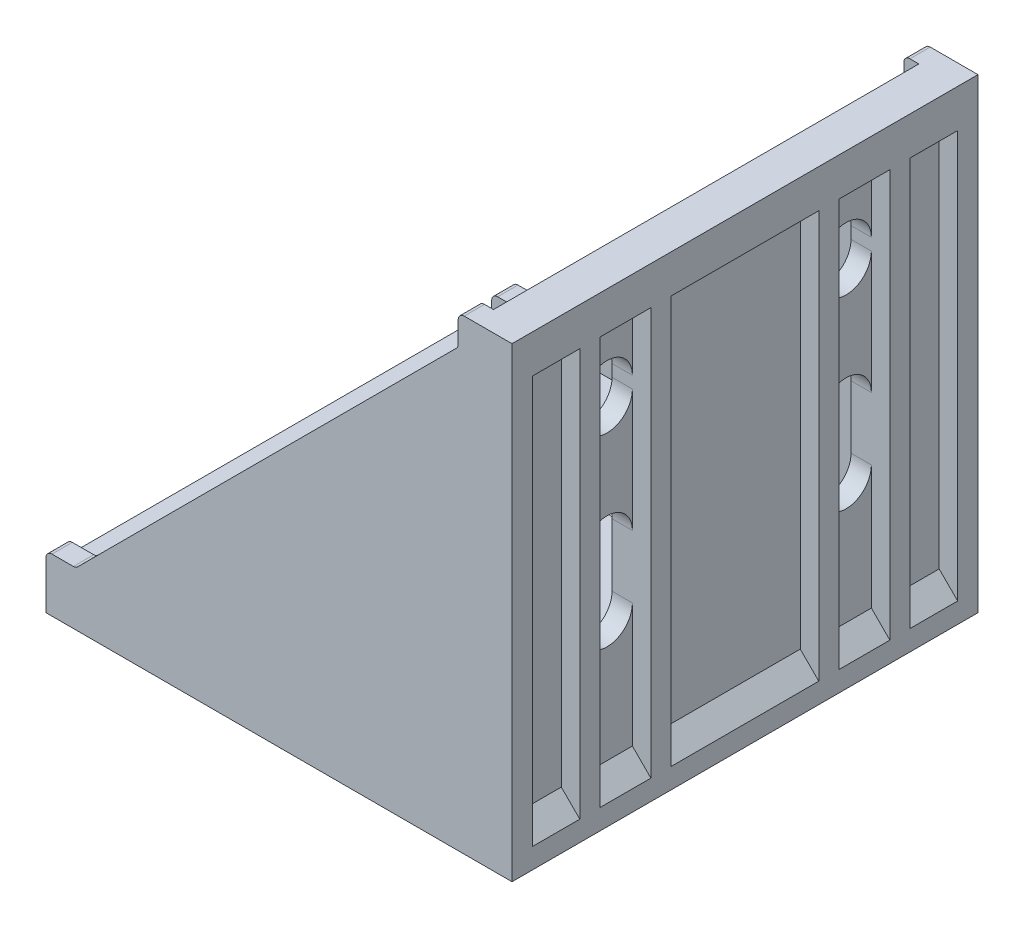
SolidWorks part; units mm, degrees
material "6061 Alloy"
ref_plane "Front Plane" through (0, 0, 0) normal (0, 0, 1) x (1, 0, 0)
ref_plane "Top Plane" through (0, 0, 0) normal (0, 1, 0) x (1, 0, 0)
ref_plane "Right Plane" through (0, 0, 0) normal (1, 0, 0) x (0, 0, -1)
sketch "Sketch1" plane through (0, 0, 0) normal (0, 0, 1) x (1, 0, 0)
  line L0 (-78, 0) -> (0, 0)
  line L1 (0, 0) -> (0, 78)
  line L2 (0, 78) -> (-9, 78)
  line L3 (-9, 78) -> (-9, 73)
  line L4 (-9, 73) -> (-73, 9)
  line L5 (-73, 9) -> (-78, 9)
  line L6 (-78, 9) -> (-78, 0)
  dimension "D1" = 78
  dimension "D2" = 5
  dimension "D3" = 9
extrude "Boss-Extrude1" add sketch "Sketch1" along normal mid plane 78
sketch "Sketch2" plane through (0, 0, 0) normal (0, 0, 1) x (1, 0, 0)
  line L0 (-6.5, 78) -> (-6.5, 6.5)
  line L1 (0, 78) -> (-9, 78) construction
  line L2 (-6.5, 6.5) -> (-78, 6.5)
  line L3 (-78, 9) -> (-78, 0) construction
  line L4 (-78, 6.5) -> (-78, 78)
  line L5 (-78, 78) -> (-6.5, 78)
  line L6 (0, 0) -> (0, 78) construction
  dimension "D1" = 6.5
extrude "Cut-Extrude1" cut sketch "Sketch2" against normal offset from surface 3.4 and the other way offset from surface 3.4 up to face at (-35.2857, 35.2857, -39) other way up to face at (-35.2857, 35.2857, 39)
sketch "Sketch3" plane through (0, 6.5, 0) normal (0, 1, 0) x (1, 0, 0)
  line L0 (-78, 0) -> (-8.1122, 0) construction
  line L1 (-78, 35.6) -> (-78, -35.6) construction
  line L2 (-42, -20) -> (-54, -20) construction
  line L3 (-27.25, -20) -> (-37.75, -20) construction
  line L4 (-27.25, -24.25) -> (-37.75, -24.25)
  line L5 (-27.25, -15.75) -> (-37.75, -15.75)
  line L6 (-60.25, -20) -> (-58.25, -20) construction
  line L7 (-60.25, -15.75) -> (-58.25, -15.75)
  line L8 (-60.25, -24.25) -> (-58.25, -24.25)
  line L9 (-64.5, -20) -> (-78, -20) construction
  line L10 (-27.25, 20) -> (-37.75, 20) construction
  line L11 (-27.25, 24.25) -> (-37.75, 24.25)
  line L12 (-27.25, 15.75) -> (-37.75, 15.75)
  line L13 (-60.25, 20) -> (-58.25, 20) construction
  line L14 (-60.25, 15.75) -> (-58.25, 15.75)
  line L15 (-60.25, 24.25) -> (-58.25, 24.25)
  arc A0 (-27.25, -24.25) -> (-27.25, -15.75) centre (-27.25, -20) ccw
  arc A1 (-37.75, -15.75) -> (-37.75, -24.25) centre (-37.75, -20) ccw
  arc A2 (-60.25, -15.75) -> (-60.25, -24.25) centre (-60.25, -20) ccw
  arc A3 (-58.25, -24.25) -> (-58.25, -15.75) centre (-58.25, -20) ccw
  arc A4 (-27.25, 24.25) -> (-27.25, 15.75) centre (-27.25, 20) cw
  arc A5 (-37.75, 15.75) -> (-37.75, 24.25) centre (-37.75, 20) cw
  arc A6 (-60.25, 15.75) -> (-60.25, 24.25) centre (-60.25, 20) cw
  arc A7 (-58.25, 24.25) -> (-58.25, 15.75) centre (-58.25, 20) cw
  point P9 (-32.5, -20)
  point P14 (-59.25, -20)
  point P25 (-32.5, 20)
  point P32 (-59.25, 20)
  dimension "D3" = 19
  dimension "D4" = 10.5
  dimension "D1" = 8.5
  dimension "D2" = 12
  dimension "D5" = 13.5
  dimension "D6" = 40
extrude "Cut-Extrude2" cut sketch "Sketch3" against normal blind 10
sketch "Sketch4" plane through (0, 0, 0) normal (0, 0, 1) x (1, 0, 0)
  line L0 (0, 0) -> (-41, 41) construction
  line L1 (-9, 73) -> (-73, 9) construction
ref_plane "Plane1" through (0, 0, 0) normal (-0.7071, -0.7071, 0) x (-0.7071, 0.7071, 0)
sketch "Sketch5" plane through (0, 0, 0) normal (0, -1, 0) x (1, 0, 0)
  line L0 (-37.75, 20) -> (-27.25, 20) construction
  line L1 (0, 0) -> (-41, 0) construction
  line L2 (-3.4, 15.75) -> (-71.6, 15.75)
  line L3 (-3.4, 15.75) -> (-3.4, 24.25)
  line L4 (-3.4, 24.25) -> (-71.6, 24.25)
  line L5 (-71.6, 15.75) -> (-71.6, 24.25)
  line L6 (-37.5, 24.25) -> (-37.5, 15.75) construction
  line L7 (-3.4, 20) -> (-71.6, 20) construction
  line L8 (-3.4, 27.65) -> (-71.6, 27.65)
  line L9 (-3.4, 27.65) -> (-3.4, 35.6)
  line L10 (-3.4, 35.6) -> (-71.6, 35.6)
  line L11 (-71.6, 27.65) -> (-71.6, 35.6)
  line L12 (-3.4, 12.35) -> (-71.6, 12.35)
  line L13 (-3.4, 12.35) -> (-3.4, -12.35)
  line L14 (-3.4, -12.35) -> (-71.6, -12.35)
  line L15 (-71.6, 12.35) -> (-71.6, -12.35)
  line L16 (-37.5, -12.35) -> (-37.5, 12.35) construction
  line L17 (-3.4, 0) -> (-71.6, 0) construction
  line L18 (-3.4, -20) -> (-71.6, -20) construction
  line L19 (-37.5, -24.25) -> (-37.5, -15.75) construction
  line L20 (-37.75, -20) -> (-27.25, -20) construction
  line L21 (-71.6, -27.65) -> (-71.6, -35.6)
  line L22 (-3.4, -35.6) -> (-71.6, -35.6)
  line L23 (-3.4, -27.65) -> (-3.4, -35.6)
  line L24 (-3.4, -27.65) -> (-71.6, -27.65)
  line L25 (-71.6, -15.75) -> (-71.6, -24.25)
  line L26 (-3.4, -24.25) -> (-71.6, -24.25)
  line L27 (-3.4, -15.75) -> (-3.4, -24.25)
  line L28 (-3.4, -15.75) -> (-71.6, -15.75)
  line L29 (-78, 35.6) -> (-6.5, 35.6) construction
  line L30 (-3.4, 39) -> (-3.4, 35.6) construction
  line L31 (-78, 39) -> (0, 39) construction
  line L32 (0, 35.6) -> (-3.4, 35.6) construction
  line L33 (0, 39) -> (0, -39) construction
  line L34 (-71.6, 12.35) -> (-71.6, 15.75) construction
  line L35 (-71.6, 24.25) -> (-71.6, 27.65) construction
  line L36 (-71.6, 27.65) -> (-71.6125, 27.7585) construction
  line L37 (-78, 39) -> (-78, -39) construction
  point P4 (-37.5, 20)
  point P12 (-37.5, 0)
  point P32 (-37.5, -20)
  dimension "D1" = 8.5
  dimension "D2" = 3.4
  dimension "D3" = 6.4
extrude "Cut-Extrude3" cut sketch "Sketch5" against normal offset from surface (3.1 mm away) 3.4 up to face at (-59.25, 6.5, -20)
chamfer "Chamfer1" distance 3.1 angle 45 5 edges at (-3.4, 3.1, 31.625) (-3.4, 3.1, 20) (-3.4, 3.1, 0) (-3.4, 3.1, -20) (-3.4, 3.1, -31.625)
mirror "Mirror1" about plane through (0, 0, 0) normal (-0.7071, -0.7071, 0) of "Cut-Extrude3", "Chamfer1", "Cut-Extrude2"
fillet "Fillet1" radius 1 8 edges at (-73, 9, 37.3) (-73, 9, -37.3) (-78, 9, 37.3) (-78, 9, -37.3) (-9, 73, 37.3) (-9, 73, -37.3) (-9, 78, 37.3) (-9, 78, -37.3)
